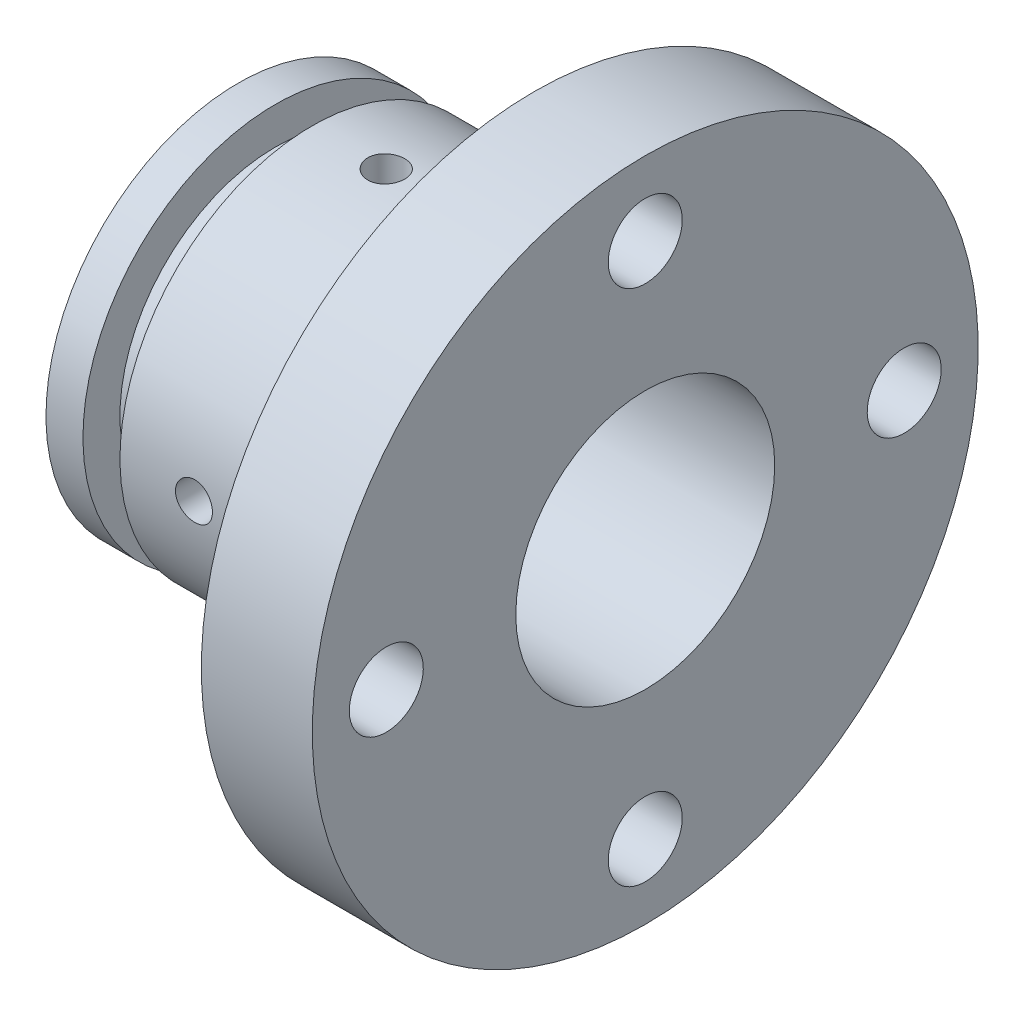
SolidWorks part; units mm, degrees
ref_plane "Front Plane" through (0, 0, 0) normal (0, 0, 1) x (1, 0, 0)
ref_plane "Top Plane" through (0, 0, 0) normal (0, 1, 0) x (1, 0, 0)
ref_plane "Right Plane" through (0, 0, 0) normal (1, 0, 0) x (0, 0, -1)
sketch "Sketch1" plane through (0, 0, 0) normal (0, 0, 1) x (1, 0, 0)
  line L0 (0, 0) -> (0, 26)
  line L1 (0, 26) -> (5, 26)
  line L2 (5, 26) -> (5, 21)
  line L3 (5, 21) -> (10, 21)
  line L4 (10, 21) -> (10, 26)
  line L5 (10, 26) -> (30, 26)
  line L6 (30, 26) -> (30, 21)
  line L7 (30, 21) -> (35, 21)
  line L8 (35, 21) -> (35, 26)
  line L9 (35, 26) -> (40, 26)
  line L10 (40, 26) -> (40, 45)
  line L11 (40, 45) -> (55, 45)
  line L12 (55, 45) -> (55, 0)
  line L13 (55, 0) -> (0, 0)
  line L14 (0, 0) -> (117.5775, 0) construction
  dimension "D1" = 26
  dimension "D2" = 45
  dimension "D3" = 5
  dimension "D4" = 5
  dimension "D5" = 5
  dimension "D6" = 20
  dimension "D7" = 5
  dimension "D8" = 5
  dimension "D9" = 15
revolve "Revolve1" add sketch "Sketch1" angle 360 about L14
sketch "Sketch2" plane through (0, 0, 0) normal (-1, 0, 0) x (0, 0, 1)
  circle A0 centre (0, 0) radius 17.5
  dimension "D1" = 35
extrude "Cut-Extrude1" cut sketch "Sketch2" against normal through all
sketch "Sketch3" plane through (55, 0, 0) normal (1, 0, 0) x (0, 0, -1)
  circle A0 centre (-35, 0) radius 5
  circle A1 centre (0, 35) radius 5
  circle A2 centre (35, 0) radius 5
  circle A3 centre (0, -35) radius 5
  point P12 (0, 0)
  dimension "D1" = 10
  dimension "D2" = 35
  dimension "D3" = 4
extrude "Cut-Extrude2" cut sketch "Sketch3" against normal through all
ref_axis "Axis1" through (30, 0, 0) along (-1, 0, 0)
ref_plane "Plane1" through (0, 26, 0) normal (0, 1, 0) x (1, 0, 0)
sketch "Sketch4" plane through (0, 26, 0) normal (0, 1, 0) x (1, 0, 0)
  line L0 (30, 0) -> (10, 0) construction
  line L1 (10, 26) -> (10, -26) construction
  circle A0 centre (20, 0) radius 2.5
  dimension "D1" = 5
  dimension "D2" = 10
extrude "Cut-Extrude3" cut sketch "Sketch4" against normal blind 5
ref_plane "Plane2" through (0, 0, 26) normal (0, 0, 1) x (1, 0, 0)
sketch "Sketch5" plane through (0, 0, 26) normal (0, 0, 1) x (1, 0, 0)
  line L0 (30, 0) -> (10, 0) construction
  line L1 (10, 26) -> (10, -26) construction
  circle A0 centre (20, 0) radius 2.5
  dimension "D1" = 5
  dimension "D2" = 10
extrude "Cut-Extrude4" cut sketch "Sketch5" against normal blind 5
ref_plane "Plane3" through (0, -26, 0) normal (0, -1, 0) x (-1, 0, 0)
sketch "Sketch6" plane through (0, -26, 0) normal (0, -1, 0) x (-1, 0, 0)
  line L0 (-30, 0) -> (-10, 0) construction
  line L1 (-10, -26) -> (-10, 26) construction
  circle A0 centre (-20, 0) radius 2.5
  dimension "D1" = 5
  dimension "D2" = 10
extrude "Cut-Extrude5" cut sketch "Sketch6" against normal blind 5
ref_plane "Plane4" through (0, 0, -26) normal (0, 0, -1) x (-1, 0, 0)
sketch "Sketch8" plane through (0, 0, -26) normal (0, 0, -1) x (-1, 0, 0)
  line L0 (-30, 0) -> (-10, 0) construction
  line L1 (-10, -26) -> (-10, 26) construction
  circle A0 centre (-20, 0) radius 2.5
  dimension "D1" = 5
  dimension "D2" = 10
extrude "Cut-Extrude6" cut sketch "Sketch8" against normal blind 5
